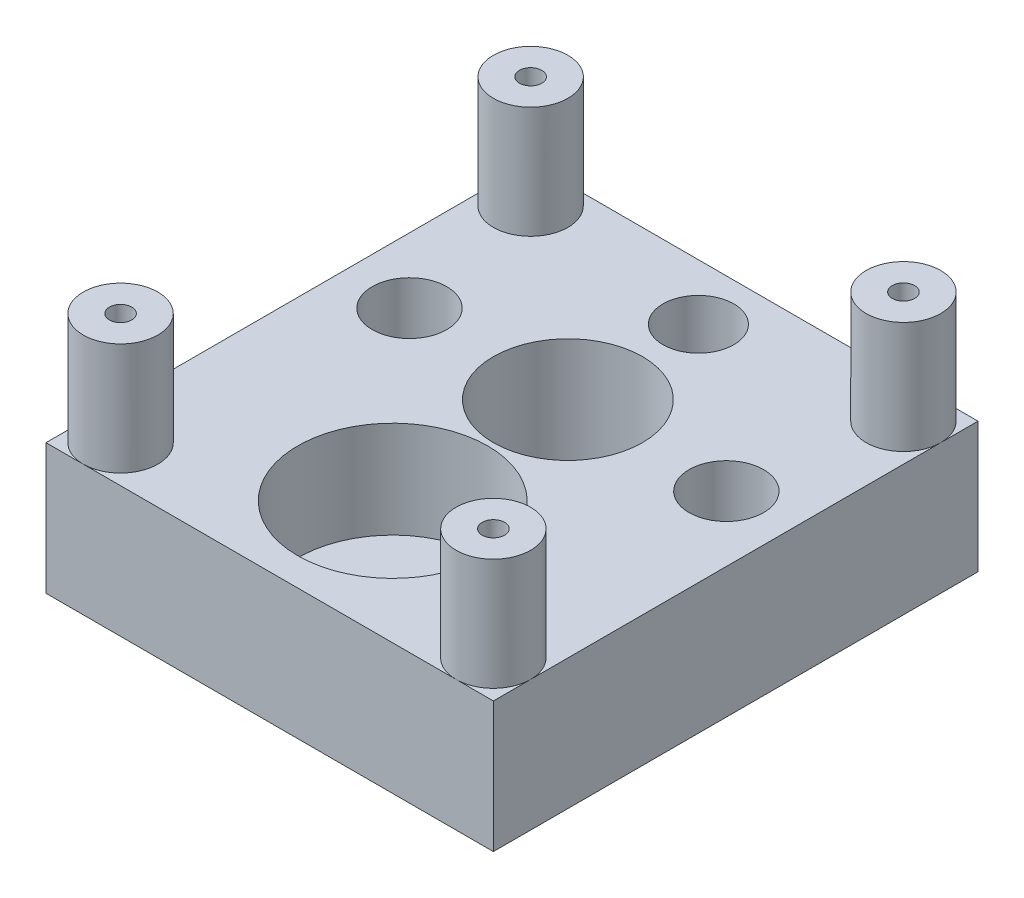
SolidWorks part; units mm, degrees
ref_plane "前视基准面" through (0, 0, 0) normal (0, 0, 1) x (1, 0, 0)
ref_plane "上视基准面" through (0, 0, 0) normal (0, 1, 0) x (1, 0, 0)
ref_plane "右视基准面" through (0, 0, 0) normal (1, 0, 0) x (0, 0, -1)
other "Configuration Table"
sketch "草图1" plane through (0, 0, 0) normal (0, 1, 0) x (1, 0, 0)
  line L0 (-4.25, 0) -> (4.25, 0)
  line L1 (-6, 5) -> (6, 5)
  line L2 (-6, 5) -> (-6, -8)
  line L3 (-6, -8) -> (6, -8)
  line L4 (6, 5) -> (6, -8)
  line L5 (0, 3.5) -> (0, 0)
  line L6 (0, 5) -> (0, -8) construction
  line L7 (-6, 5) -> (-6, -8) construction
  circle A0 centre (0, 0) radius 2
  circle A1 centre (-4.25, 0) radius 0.8
  circle A2 centre (4.25, 0) radius 0.8
  circle A3 centre (0, 3.5) radius 0.7
  circle A4 centre (-4.25, 0) radius 1
  circle A5 centre (4.25, 0) radius 1
  circle A6 centre (0, 3.5) radius 0.95
  dimension "D1" = 1.4
  dimension "D2" = 1.6
  dimension "D3" = 4
  dimension "D6" = 1.9
  dimension "D7" = 2
  dimension "D4" = 8.5
  dimension "D5" = 3.5
  dimension "D8" = 0
  dimension "D9" = 8
  dimension "D10" = 6
  dimension "D11" = 12
  dimension "D12" = 5
extrude "凸台-拉伸1" add sketch "草图1" along normal blind 3.5 contours L1 L4 L3 L2 | A0 | A1 | A2 | A3
extrude "切除-拉伸2" cut sketch "草图1<3>" against normal blind 1.5 from surface contours A4 | A6 | A5 starting at face at (4.25, 3.5, 0.8)
sketch "草图1<3>" plane through (0, 0, 0) normal (0, 1, 0) x (1, 0, 0) same geometry as "草图1"
sketch "草图2" plane through (0, 3.5, 0) normal (0, 1, 0) x (1, 0, 0)
  circle A0 centre (0, -4.7) radius 2.55
  dimension "D1" = 5.1
  dimension "D2" = 4.7
extrude "切除-拉伸5" cut sketch "草图2" against normal blind 2.6
sketch "草图3" plane through (0, 3.5, 0) normal (0, 1, 0) x (1, 0, 0)
  line L5 (-6, 5) -> (6, 5) construction
  line L6 (6, 5) -> (6, -8) construction
  line L7 (-6, 5) -> (-6, -8) construction
  line L10 (-6, -8) -> (6, -8) construction
  circle A0 centre (-5, -7) radius 1
  circle A1 centre (5, 4) radius 1
  circle A3 centre (5, 4) radius 0.3
  circle A4 centre (-5, -7) radius 0.3
  circle A5 centre (-5, 4) radius 1
  circle A6 centre (-5, 4) radius 0.3
  circle A7 centre (5, -7) radius 1
  circle A8 centre (5, -7) radius 0.3
  dimension "D1" = 2
  dimension "D2" = 0.6
  dimension "D3" = 12
extrude "凸台-拉伸2" add sketch "草图3" along normal blind 3 contours A0 | A1 | A5 | A7
extrude "切除-拉伸6" cut sketch "草图3<3>" against normal blind 2 from surface contours A4 | A3 | A6 | A8 starting at face at (-5, 6.5, 8)
sketch "草图3<3>" plane through (0, 3.5, 0) normal (0, 1, 0) x (1, 0, 0) same geometry as "草图3"
